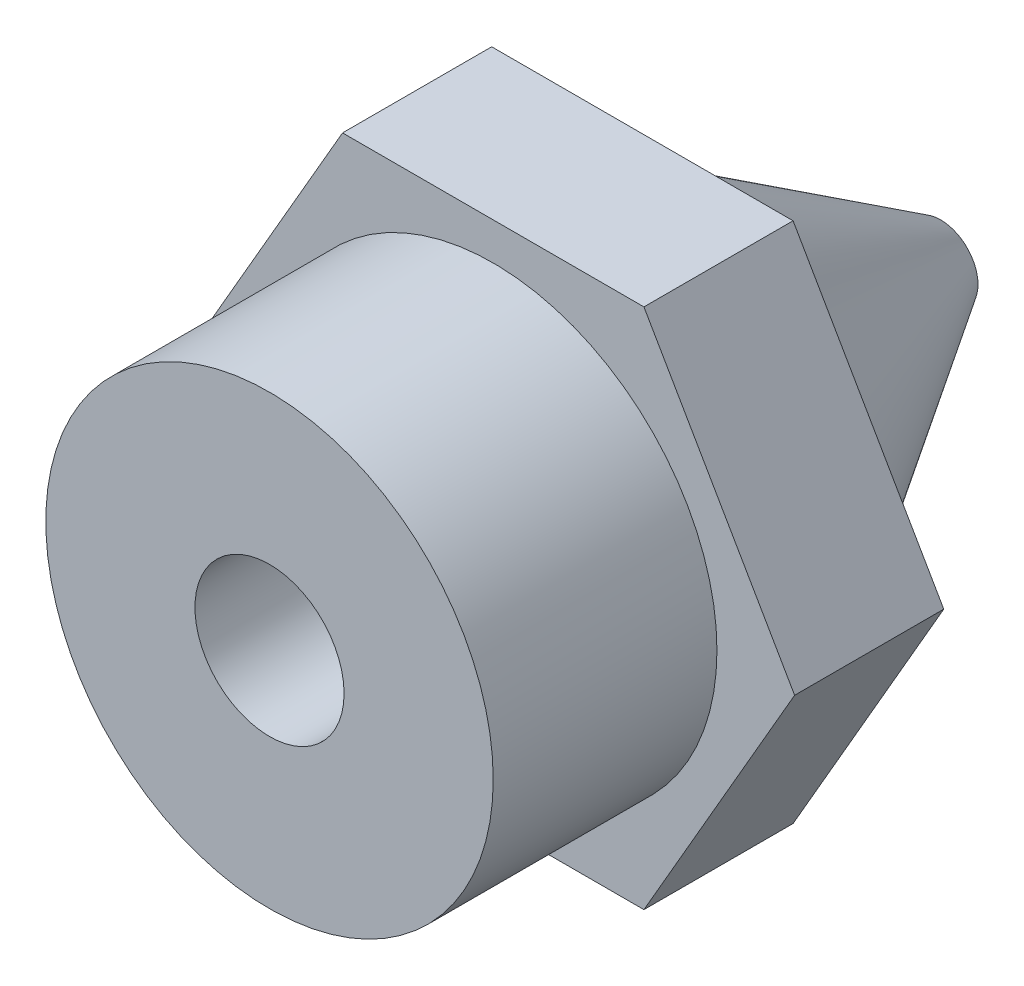
SolidWorks part; units mm, degrees
material "Laiton"
ref_plane "Plan de face" through (0, 0, 0) normal (0, 0, 1) x (1, 0, 0)
ref_plane "Plan de dessus" through (0, 0, 0) normal (0, 1, 0) x (1, 0, 0)
ref_plane "Plan de droite" through (0, 0, 0) normal (1, 0, 0) x (0, 0, -1)
sketch "Esquisse1" plane through (0, 0, 0) normal (0, 0, 1) x (1, 0, 0)
  line L1 (4.0415, 0) -> (2.0207, 3.5)
  line L2 (2.0207, 3.5) -> (-2.0207, 3.5)
  line L3 (-2.0207, 3.5) -> (-4.0415, 0)
  line L4 (-4.0415, 0) -> (-2.0207, -3.5)
  line L5 (-2.0207, -3.5) -> (2.0207, -3.5)
  line L6 (2.0207, -3.5) -> (4.0415, 0)
  circle A0 centre (0, 0) radius 3.5 construction
  dimension "D1" = 7
extrude "Boss.-Extru.1" add sketch "Esquisse1" along normal blind 9 contours L3 L4 L5 L6 L1 L2
sketch "Esquisse2" plane through (0, 0, 9) normal (0, 0, 1) x (1, 0, 0)
  line L1 (-9.4849, 6.2226) -> (10.1391, 6.2226)
  line L2 (-9.4849, 6.2226) -> (-9.4849, -9.3115)
  line L3 (-9.4849, -9.3115) -> (10.1391, -9.3115)
  line L4 (10.1391, 6.2226) -> (10.1391, -9.3115)
  circle A0 centre (0, 0) radius 3
  dimension "D1" = 6
extrude "Enlèv. mat.-Extru.1" cut sketch "Esquisse2" against normal blind 3
cosmetic thread "Représentation de filetage1" parameters "D1"=3, "D2"=4.891
sketch "Esquisse3" plane through (0, 0, 0) normal (0, 0, -1) x (-1, 0, 0)
  line L1 (5.6434, -6.9413) -> (-5.6238, -6.9413)
  line L2 (5.6434, -6.9413) -> (5.6434, 7.0198)
  line L3 (5.6434, 7.0198) -> (-5.6238, 7.0198)
  line L4 (-5.6238, -6.9413) -> (-5.6238, 7.0198)
  circle A0 centre (0, 0) radius 3
  dimension "D1" = 6
extrude "Enlèv. mat.-Extru.2" cut sketch "Esquisse3" against normal blind 4
chamfer "Chanfrein1" distance 4 angle 32 1 edges at (-3, 0, 0) first distance on face at (-3, 0, 4)
sketch "Esquisse4" plane through (0, 0, 0) normal (0, 1, 0) x (1, 0, 0)
  line L0 (0, -10.3816) -> (0, 2.1166) construction
  line L1 (0, -9) -> (1, -9)
  line L2 (-3, -9) -> (3, -9) construction
  line L3 (0, 0) -> (0.3, 0)
  line L4 (0.3, 0) -> (1, -5.701)
  line L5 (0, -9) -> (0, 0)
  line L9 (1, -5.701) -> (1, -9)
  dimension "D1" = 1
  dimension "D2" = 0.3
  dimension "D3" = 7
  dimension "D4" = 3.299
revolve "Enlèvement de matière-Révolution1" cut sketch "Esquisse4" angle 360 about L0
